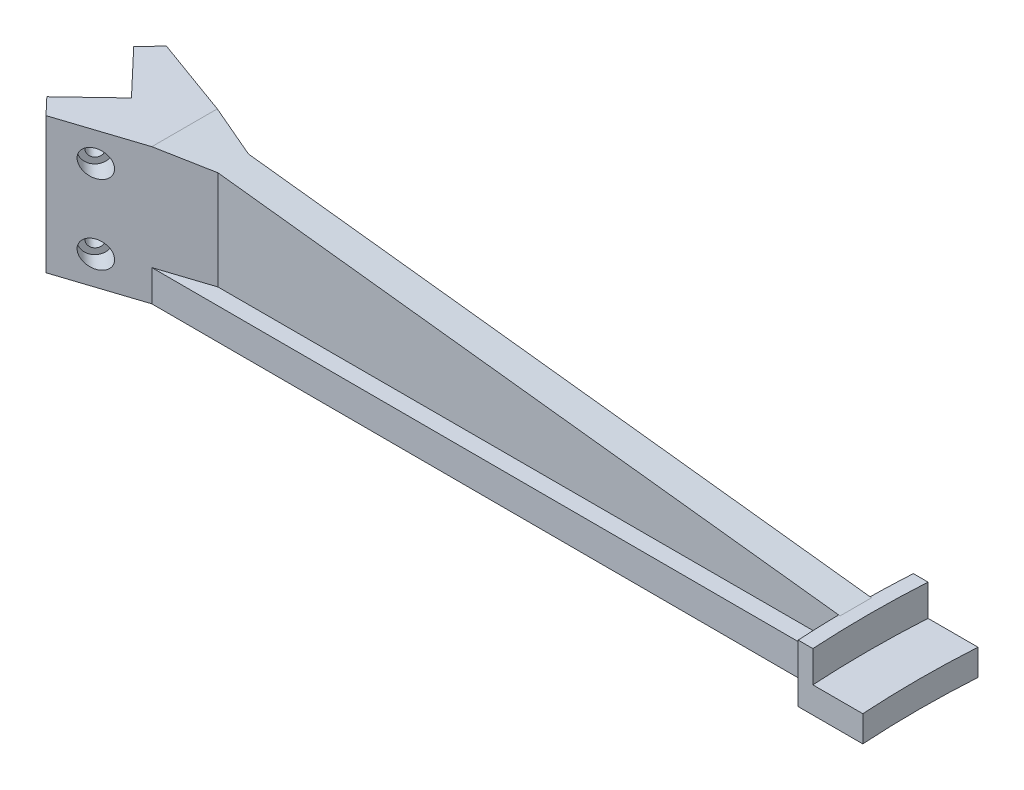
SolidWorks part; units mm, degrees
ref_plane "Front Plane" through (0, 0, 0) normal (0, 0, 1) x (1, 0, 0)
ref_plane "Top Plane" through (0, 0, 0) normal (0, 1, 0) x (1, 0, 0)
ref_plane "Right Plane" through (0, 0, 0) normal (1, 0, 0) x (0, 0, -1)
sketch "Sketch2" plane through (0, 0, 0) normal (0, 1, 0) x (1, 0, 0)
  line L0 (0, 0) -> (-276.0246, 0) construction
  line L1 (0, 0) -> (135.9511, 0) construction
  line L2 (-276.0246, 0) -> (-292.5966, 15.7434)
  line L3 (-292.5966, 15.7434) -> (-286.5108, 22.1496)
  line L4 (-286.5108, 22.1496) -> (-276.0246, 12.1877)
  line L5 (-276.0246, 12.1877) -> (-276.0246, 0)
  line L14 (0.6536, 22) -> (25.3402, 22)
  line L15 (0.6536, -22) -> (25.3402, -22)
  line L16 (25.3402, 22) -> (25.3402, -22) construction
  line L34 (-276.0246, 0) -> (-292.5966, -17.4443)
  line L49 (-292.5966, -17.4443) -> (-286.5108, -23.8504)
  line L50 (-286.5108, -23.8504) -> (-276.0246, -12.8123)
  line L51 (-276.0246, -12.8123) -> (-276.0246, 0)
  line L52 (-276.0246, 12.1877) -> (0.2109, 12.5)
  line L53 (-276.0246, -12.8123) -> (0.2109, -12.5)
  line L54 (0.2109, -12.5) -> (0.2109, 12.5) construction
  line L55 (-276.0246, 12.1877) -> (-276.0246, 24.2548) construction
  line L56 (-276.0246, -12.8123) -> (-276.0246, -19.1381)
  line L58 (-286.5108, 22.1496) -> (-256.0246, 12.2103)
  line L62 (-286.5108, -23.8504) -> (-256.0246, -12.7897)
  line L63 (-256.0246, 12.2103) -> (-256.0246, -12.7897)
  line L64 (-256.0246, -12.7897) -> (-219.7315, 0.3778)
  line L65 (-256.0246, 12.2103) -> (-219.7315, 0.3778)
  arc A0 (0.6536, 22) -> (0.6536, -22) centre (370.6, 0) ccw
  arc A1 (6.2636, 22) -> (6.2636, -22) centre (370.6, 0) ccw
  arc A2 (25.3402, 22) -> (25.3402, -22) centre (370.6, 0) ccw
  point P32 (5.6, 0)
  dimension "D2" = 365
  dimension "D3" = 5.6
  dimension "D4" = 19.04
  dimension "D7" = 25
  dimension "D5" = 133.531
  dimension "D6" = 136.469
  dimension "D8" = 25
  dimension "D9" = 44
  dimension "D10" = 20
  dimension "D18" = 46
  dimension "D19" = 281.6246
extrude "Boss-Extrude2" add sketch "Sketch2" against normal blind 12 contours A0 L52 L53 | L53 L52 | L53 | L52 | A1 L14 A0 L15 | L50 L51 L34 L49 | L5 L4 L3 L2 | L65 L63 L64 region at (-282.9032, 0, -12.1717) region at (-282.9032, 0, 13.1665) region at (-266.0246, 0, 0.301) region at (-272.8533, 0, -15.5159) region at (-272.8533, 0, 16.4841) region at (-243.9269, 0, 0.0672) region at (-119.1345, 0, 0.1509) region at (3.0196, 0, 0)
extrude "Boss-Extrude3" add sketch "Sketch2<5>" along normal blind 10 from surface contours A2 L14 A1 L15 region at (15.3473, 0, 0) starting at face at (-148.6736, -12, 0.3062)
sketch "Sketch2<5>" plane through (0, 0, 0) normal (0, 1, 0) x (1, 0, 0) same geometry as "Sketch2"
extrude "Boss-Extrude4" add sketch "Sketch2<6>" along normal blind 22 from surface contours A1 L14 A0 L15 region at (3.0196, 0, 0) starting at face at (-145.7416, -12, 0.3062)
sketch "Sketch2<6>" plane through (0, 0, 0) normal (0, 1, 0) x (1, 0, 0) same geometry as "Sketch2"
extrude "Boss-Extrude7" add sketch "Sketch2<9>" along normal blind 40 contours L63 L52 L5 L51 L53 | L5 L4 L3 L2 | L58 L4 L52 | L50 L51 L34 L49 | L50 L62 L53 | L65 L63 L64 region at (-282.9032, 0, -12.1717) region at (-282.9032, 0, 13.1665) region at (-266.0246, 0, 0.301) region at (-272.8533, 0, -15.5159) region at (-272.8533, 0, 16.4841) region at (-243.9269, 0, 0.0672)
sketch "Sketch2<9>" plane through (0, 0, 0) normal (0, 1, 0) x (1, 0, 0) same geometry as "Sketch2"
sketch "Sketch4" plane through (0, 0, 0) normal (0, 0, 1) x (1, 0, 0)
  line L2 (-292.5966, -12) -> (-292.5966, 40) construction
  line L5 (0.6536, 10) -> (-256.0246, 40)
  line L6 (-286.5108, 40) -> (-219.7315, 40) construction
  line L8 (-276.0246, 0) -> (0.2109, 0) construction
  line L9 (-256.0246, 0) -> (0.6536, 0)
  line L10 (0.6536, 0) -> (0.6536, 10)
  line L11 (0.6536, -12) -> (0.6536, 10) construction
  line L12 (0.6536, 10) -> (0, 10) construction
  line L13 (-256.0246, 40) -> (-256.0246, 0)
  dimension "D1" = 36.572
extrude "Boss-Extrude17" add sketch "Sketch4" along normal blind 6 and the other way blind 6
sketch "Sketch5" plane through (0, 0, 0) normal (0, 0, 1) x (1, 0, 0)
  line L0 (0.6536, 10) -> (-256.0246, 40) construction
  line L1 (0.6536, 10) -> (-256.0246, 40)
extrude "Cut-Extrude-Thin1" cut sketch "Sketch5" against normal through all and the other way through all thin contours L1 thin type one direction wall 10
sketch "Sketch6" plane through (-145.0852, 0, -137.8309) normal (-0.725, 0, -0.6887) x (-0.6887, 0, 0.725)
  line L0 (200.1118, 29) -> (200.1118, -1) construction
  line L1 (190.1118, 40) -> (214.1728, 40) construction
  line L2 (190.1118, 40) -> (210.1118, 40)
  line L3 (190.1118, 40) -> (190.1118, -12)
  line L4 (190.1118, -12) -> (210.1118, -12)
  line L5 (210.1118, 40) -> (210.1118, -12)
  line L6 (190.1118, 40) -> (210.1118, -12) construction
  line L7 (190.1118, -12) -> (210.1118, 40) construction
  line L8 (190.1118, -12) -> (190.1118, 40) construction
  line L9 (190.1118, -12) -> (214.1728, -12) construction
  circle A0 centre (200.1118, 29) radius 5
  circle A1 centre (200.1118, -1) radius 5
  circle A2 centre (200.1118, 29) radius 2.75
  circle A3 centre (200.1118, -1) radius 2.75
  point P3 (200.1118, 14)
  point P6 (200.1118, 14)
  dimension "D2" = 10
  dimension "D3" = 5.5
  dimension "D1" = 20
  dimension "D4" = 30
extrude "Cut-Extrude1" cut sketch "Sketch6" against normal through all from offset 8 contours A0 | A1 offset against normal yes
extrude "Cut-Extrude2" cut sketch "Sketch6<4>" against normal through all both and the other way through all contours A2 | A3
sketch "Sketch6<4>" plane through (-145.0852, 0, -137.8309) normal (-0.725, 0, -0.6887) x (-0.6887, 0, 0.725) same geometry as "Sketch6"
mirror "Mirror1" about plane through (0, 0, 0) normal (0, 0, 1) of "Cut-Extrude1", "Cut-Extrude2"
ref_plane "Plane1" through (0, 0, -40) normal (0, 0, 1) x (1, 0, 0)
mirror "Mirror4" about plane through (0, 0, -40) normal (0, 0, 1) of bodies 120
delete or keep bodies "-1" type delete bodies bodies 120
